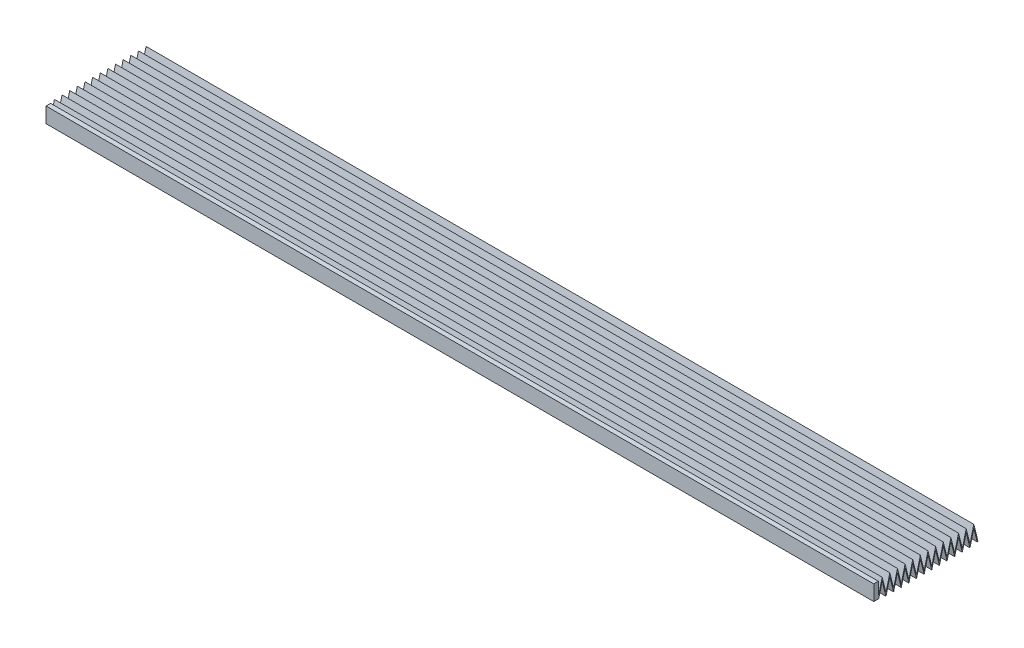
SolidWorks part; units mm, degrees
ref_plane "Front Plane" through (0, 0, 0) normal (0, 0, 1) x (1, 0, 0)
ref_plane "Top Plane" through (0, 0, 0) normal (0, 1, 0) x (1, 0, 0)
ref_plane "Right Plane" through (0, 0, 0) normal (1, 0, 0) x (0, 0, -1)
sketch "Sketch2" plane through (0, 0, 0) normal (0, 0, 1) x (1, 0, 0)
  line L1 (-270, 10) -> (270, 10)
  line L2 (-270, 10) -> (-270, 0)
  line L3 (-270, 0) -> (270, 0)
  line L4 (270, 10) -> (270, 0)
  point P4 (0, 0)
  dimension "D1" = 10
  dimension "D2" = 540
extrude "Boss-Extrude1" add sketch "Sketch2" along normal blind 3
sketch "Sketch3" plane through (270, 0, 0) normal (1, 0, 0) x (0, 0, -1)
  line L0 (0, 10) -> (64.7639, 10) construction
  line L1 (0, 0) -> (64.7639, 0) construction
  line L3 (0, 0) -> (2.4909, 10)
  line L4 (2.4909, 10) -> (4.9818, 0)
  line L5 (4.9818, 0) -> (7.4728, 10)
  line L6 (7.4728, 10) -> (9.9637, 0)
  line L7 (9.9637, 0) -> (12.4546, 10)
  line L8 (12.4546, 10) -> (14.9455, 0)
  line L9 (14.9455, 0) -> (17.4364, 10)
  line L10 (17.4364, 10) -> (19.9273, 0)
  line L11 (19.9273, 0) -> (22.4183, 10)
  line L12 (22.4183, 10) -> (24.9092, 0)
  line L13 (24.9092, 0) -> (27.4001, 10)
  line L14 (27.4001, 10) -> (29.891, 0)
  line L15 (29.891, 0) -> (32.3819, 10)
  line L16 (32.3819, 10) -> (34.8729, 0)
  line L17 (34.8729, 0) -> (37.3638, 10)
  line L18 (37.3638, 10) -> (39.8547, 0)
  line L20 (39.8547, 0) -> (42.3456, 10)
  line L21 (42.3456, 10) -> (44.8365, 0)
  line L22 (44.8365, 0) -> (47.3275, 10)
  line L23 (47.3275, 10) -> (49.8184, 0)
  line L24 (49.8184, 0) -> (52.3093, 10)
  line L25 (52.3093, 10) -> (54.8002, 0)
  line L26 (54.8002, 0) -> (57.2911, 10)
  line L27 (57.2911, 10) -> (59.782, 0)
  line L28 (59.782, 0) -> (62.273, 10)
  line L29 (62.273, 10) -> (64.7639, 0)
  line L30 (64.7639, 10) -> (64.7639, 0) construction
  line L32 (64.7639, 10) -> (64.7639, 0) construction
extrude "Extrude-Thin1" add sketch "Sketch3" against normal through all thin thin type mid plane wall 0.5
